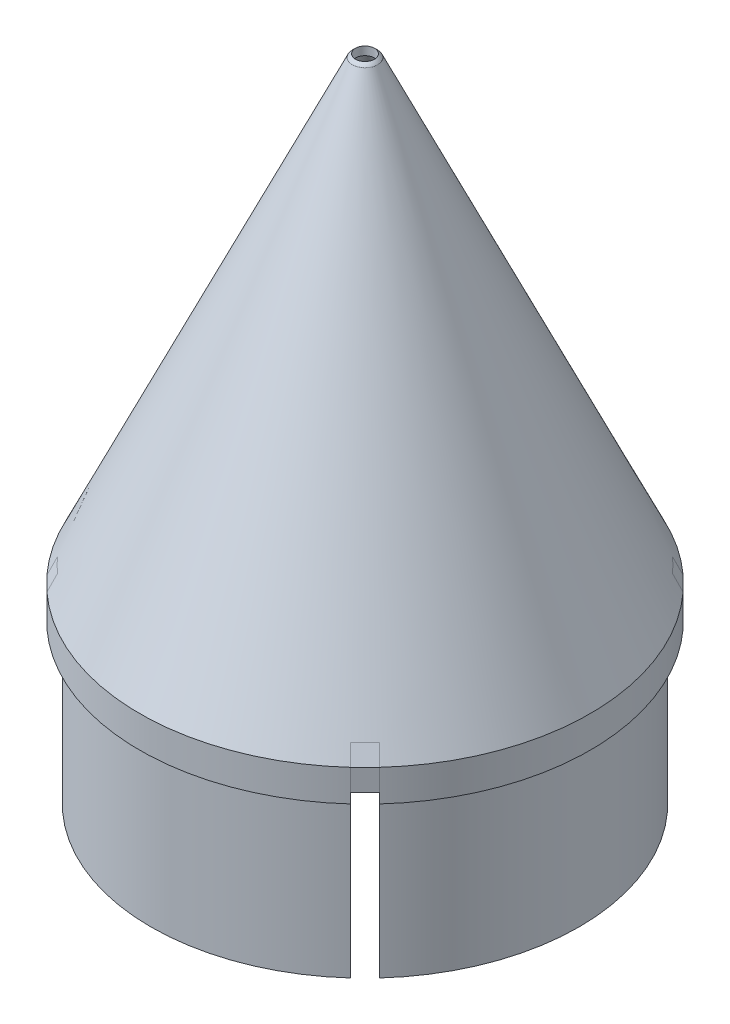
SolidWorks part; units mm, degrees
ref_plane "Front Plane" through (0, 0, 0) normal (0, 0, 1) x (1, 0, 0)
ref_plane "Top Plane" through (0, 0, 0) normal (0, 1, 0) x (1, 0, 0)
ref_plane "Right Plane" through (0, 0, 0) normal (1, 0, 0) x (0, 0, -1)
sketch "Sketch3" plane through (0, 0, 0) normal (0, 0, 1) x (1, 0, 0)
  line L1 (0, 0) -> (0, 155.682)
  line L4 (0, 0) -> (0, -50)
  line L5 (0, -50) -> (67.5, -50)
  line L6 (67.5, -50) -> (67.5, 0)
  line L9 (71, 0) -> (71, 10)
  line L11 (67.5, 0) -> (71, 0)
  line L12 (4, 153.682) -> (71, 10)
  line L13 (0, 229.1763) -> (0, 65.794) construction
  arc A0 (0, 155.682) -> (4, 153.682) centre (0, 150.682) cw
  point P11 (67.5, -50)
  point P14 (71, 10)
  dimension "Round yDim" = 2
  dimension "Lip Height" = 10
  dimension "Shoulder Height" = 50
  dimension "Half Angle" = 25
  dimension "Shoulder Diam" = 135
  dimension "Outer Diam" = 142
  dimension "Round xDim" = 8
revolve "Revolve1" add sketch "Sketch3" angle 360 about L1
shell "Shell1" thickness 1.6 removed face at (0, -50, -67.5)
sketch "Sketch7" plane through (0, 0, 0) normal (0, 1, 0) x (1, 0, 0)
  circle A0 centre (0, 0) radius 3
  dimension "D1" = 6
extrude "Cut-Extrude3" cut sketch "Sketch7" along normal through all
ref_plane "Plane1" through (0, 0, 0) normal (1, 0, 0) x (0, 0, -1)
sketch "Sketch8" plane through (0, 0, 0) normal (1, 0, 0) x (0, 0, -1)
  line L0 (-39.807, 40.9099) -> (-39.807, 20) construction
  line L1 (-44.807, 44.0901) -> (-44.807, 39.0901) construction
  line L2 (-44.807, 39.0901) -> (-39.807, 40.9099) construction
  line L3 (-39.807, 40.9099) -> (-39.807, 35.9099)
  line L4 (-44.807, 44.0901) -> (-44.807, 39.0901)
  line L5 (-44.807, 39.0901) -> (-39.807, 40.9099)
  line L6 (-39.807, 35.9099) -> (-44.807, 34.0901)
  line L7 (-44.807, 34.0901) -> (-58.0012, 34.0901)
  line L8 (-3, 152.0405) -> (-69.4, 9.6453) construction
  line L9 (-58.0012, 34.0901) -> (-44.807, 62.3852)
  line L10 (-44.807, 62.3852) -> (-44.807, 44.0901)
  dimension "D1" = 5
extrude "Boss-Extrude1" add sketch "Sketch8" along normal mid plane 15
sketch "Sketch9" plane through (0, 0, 0) normal (1, 0, 0) x (0, 0, -1)
  line L0 (-44.807, 39.0901) -> (-44.807, 61.0484) construction
  line L1 (-39.807, 40.9099) -> (-44.807, 39.0901) construction
  line L2 (-39.807, 35.9099) -> (-39.807, 40.9099) construction
  line L3 (-44.807, 34.0901) -> (-39.807, 35.9099) construction
  line L5 (-44.807, 39.0901) -> (-44.807, 61.0484)
  line L6 (-39.807, 40.9099) -> (-44.807, 39.0901)
  line L7 (-39.807, 35.9099) -> (-39.807, 40.9099)
  line L8 (-44.807, 34.0901) -> (-39.807, 35.9099)
  line L9 (-57.1133, 26.985) -> (-44.807, 34.0901)
  line L10 (-44.807, 34.0901) -> (-44.807, 39.0901) construction
  line L11 (-44.807, 61.0484) -> (-57.1133, 26.985)
  dimension "D1" = 120
extrude "Cut-Extrude4" cut sketch "Sketch9" against normal mid plane 3.5
pattern_circular "CirPattern1" count 2 over 360 about axis through (0, 0, 0) along (0, -1, 0) of "Boss-Extrude1", "Cut-Extrude4"
ref_axis "Axis1" through (0, 0, 0) along (0, -1, 0)
ref_plane "Plane2" through (0, 0, 0) normal (0.7071, 0, 0.7071) x (0, -1, 0)
sketch "Sketch11" plane through (0, 0, 0) normal (0.7071, 0, 0.7071) x (0, -1, 0)
  line L0 (-11.8535, 58.9622) -> (-14.8535, 64.1583) construction
  line L1 (-14.8535, 64.1583) -> (2.467, 74.1583) construction
  line L2 (2.467, 74.1583) -> (5.467, 68.9622) construction
  line L3 (5.467, 68.9622) -> (-11.8535, 58.9622) construction
  line L4 (-13.3535, 61.5603) -> (3.967, 71.5603) construction
  line L5 (-8.3535, 65.9) -> (-1.6, 65.9) construction
  line L6 (-15.1071, 52.9) -> (-15.1071, 66.8531)
  line L7 (-15.1071, 66.8531) -> (-9.6453, 69.4)
  line L8 (-8.3535, 52.9) -> (-13.8476, 64.682) construction
  line L9 (-13.8476, 64.682) -> (-14.9041, 66.9478) construction
  line L10 (-9.6453, 69.4) -> (-152.0405, 3) construction
  line L11 (-9.6453, 69.4) -> (-1.6, 69.4)
  line L15 (0, 0) -> (50, 0) construction
  line L16 (-1.6, 52.9) -> (-1.6, 65.9)
  line L17 (-1.6, 65.9) -> (-1.6, 69.4)
  circle A2 centre (-8.3535, 52.9) radius 13 construction
  circle A3 centre (-8.3535, 52.9) radius 10 construction
  arc A4 (-15.1071, 52.9) -> (-1.6, 52.9) centre (-8.3535, 52.9) ccw
  point P6 (-13.3535, 61.5603)
  dimension "D1" = 20
  dimension "D2" = 6
  dimension "D3" = 20
  dimension "D4" = 2.5
  dimension "LegAngle" = 30
extrude "Boss-Extrude3" add sketch "Sketch11" along normal mid plane 18
sketch "Sketch13" plane through (0, -50, 0) normal (0, -1, 0) x (1, 0, 0)
  line L0 (38.9944, -26.2665) -> (26.2665, -38.9944) construction
  line L1 (30.3324, -34.9286) -> (34.9286, -30.3324)
  line L2 (30.3324, -34.9286) -> (47.8539, -52.4501)
  line L3 (34.9286, -30.3324) -> (52.4501, -47.8539)
  arc A0 (47.8539, -52.4501) -> (52.4501, -47.8539) centre (0, 0) ccw
  circle A1 centre (0, 0) radius 71 construction
  point P11 (32.6305, -32.6305)
  point P12 (32.6305, -32.6305)
  dimension "D1" = 6.5
extrude "Cut-Extrude8" cut sketch "Sketch13" against normal up to surface (65.1071 mm away) up to face at (42.2315, 15.1071, -42.2315)
hole_wizard "M4 Clearance Hole1" positions "Sketch14" profile "Sketch15" hole size "M4" standard "ANSI Metric"
sketch "Sketch14" plane through (6.364, 0, 6.364) normal (0.7071, 0, 0.7071) x (0.7071, 0, -0.7071)
  arc A0 (52.9, 15.1071) -> (52.9, 1.6) centre (52.9, 8.3535) ccw construction
  point P0 (52.9, 8.3535)
sketch "Sketch15" plane through (43.7699, 8.3535, -31.042) normal (0, 1, 0) x (0.7071, 0, -0.7071)
  line L0 (0, 0) -> (0, 19.4421)
  line L1 (0, 19.4421) -> (2.4, 18)
  line L2 (2.4, 18) -> (2.4, 0)
  line L5 (2.4, 0) -> (0, 0)
  line L10 (0, 19.4421) -> (-2.4, 18) construction
  line L11 (0, -6.35) -> (0, 107.95) construction
  dimension "Hole Dia." = 4.8
  dimension "Hole Depth" = 18
  dimension "Drill Angle" = 118
sketch "Sketch17" plane through (0, 0, 0) normal (0.7071, 0, 0.7071) x (0, -1, 0)
  line L0 (-15.1071, 66.8531) -> (-152.0405, 3) construction
  line L1 (-47.0037, 51.9795) -> (-45.1911, 52.8247)
  line L8 (-47.0037, 51.9795) -> (-46.3473, 50.5717)
  line L9 (-45.1911, 52.8247) -> (-44.5346, 51.417)
  arc A0 (-46.3473, 50.5717) -> (-44.5346, 51.417) centre (-45.441, 50.9944) ccw
  circle A1 centre (-45.441, 50.9944) radius 0.25
  dimension "D1" = 1
  dimension "D2" = 0.5
extrude "Boss-Extrude4" add sketch "Sketch17" along normal mid plane 2.5
pattern_circular "CirPattern4" count 4 over 360 about axis through (0, 0, 0) along (0, -1, 0) of "M4 Clearance Hole1", "Cut-Extrude8", "Boss-Extrude3", "Boss-Extrude4"
sketch "Sketch18" plane through (2.2981, 0, -6.8943) normal (0.7071, 0, 0.7071) x (0.7071, 0, -0.7071)
  line L0 (62.0415, 15.1071) -> (64.4256, 10)
  line L1 (64.4256, 10) -> (64.4256, 3.1323)
  line L2 (64.4256, 10) -> (64.4256, 0) construction
  line L3 (64.4256, 3.1323) -> (61.9256, 7.4624)
  line L4 (67.6583, -2.467) -> (57.6583, 14.8535) construction
  line L6 (60.2741, 15.1071) -> (62.0415, 15.1071)
  line L7 (61.9256, 7.4624) -> (61.9256, 2.0981) construction
  circle A1 centre (46.4, 8.3535) radius 15 construction
  circle A3 centre (46.4, 8.3535) radius 2.4 construction
  arc A4 (59.3904, 14.8535) -> (58.5244, 16.3535) centre (58.5244, 15.3535) ccw construction
  arc A6 (61.9256, 7.4624) -> (60.2741, 15.1071) centre (43.4066, 7.4624) ccw
  point P10 (60.5528, 15.1071)
  dimension "D1" = 5
extrude "Boss-Extrude6" add sketch "Sketch18" along normal blind 6.5
pattern_circular "CirPattern8" count 4 over 360 about axis through (0, 0, 0) along (0, -1, 0) of "Boss-Extrude6"
equation "\"LegAngle\"=30"
